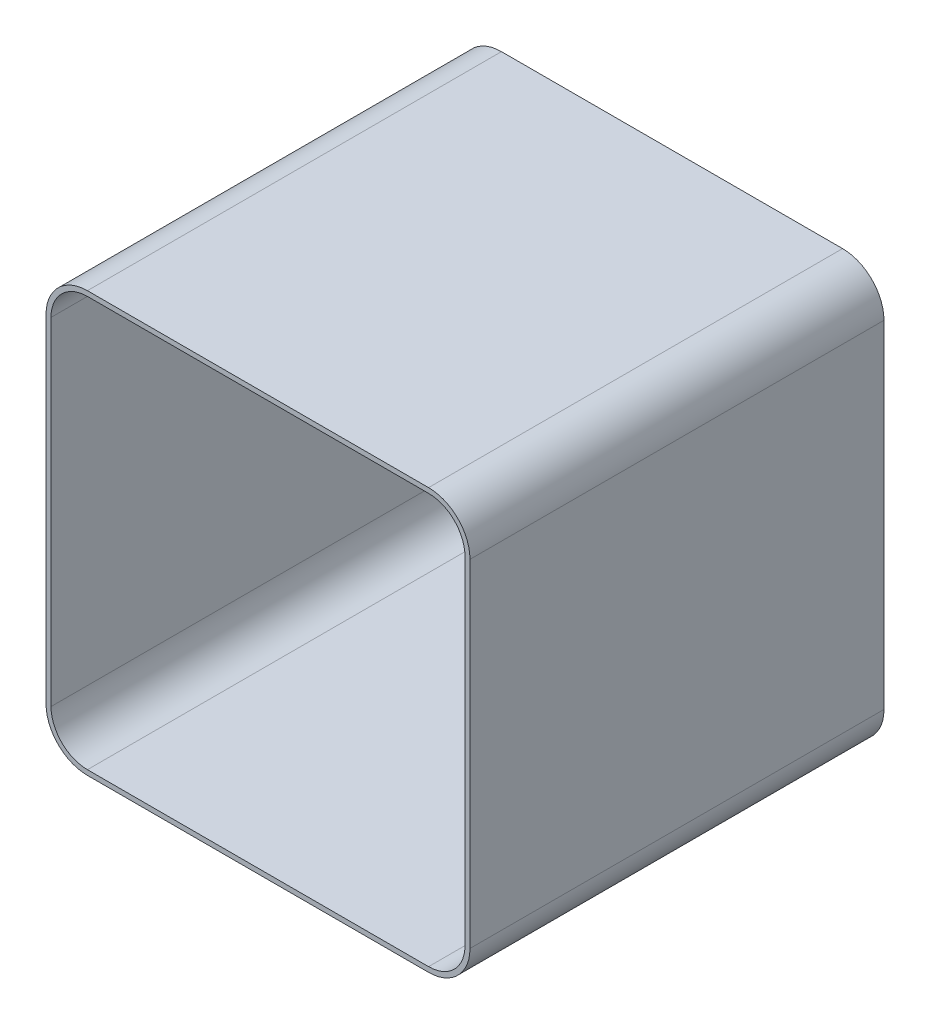
SolidWorks part; units mm, degrees
ref_plane "Front Plane" through (0, 0, 0) normal (0, 0, 1) x (1, 0, 0)
ref_plane "Top Plane" through (0, 0, 0) normal (0, 1, 0) x (1, 0, 0)
ref_plane "Right Plane" through (0, 0, 0) normal (1, 0, 0) x (0, 0, -1)
sketch "Sketch1" plane through (0, 0, 0) normal (0, 0, 1) x (1, 0, 0)
  line L1 (-358.8347, 432.2498) -> (53.1653, 432.2498)
  line L2 (-402.8347, 388.2498) -> (-402.8347, -18.7502)
  line L3 (-358.8347, -62.7502) -> (53.1653, -62.7502)
  line L4 (97.1653, 388.2498) -> (97.1653, -18.7502)
  line L5 (-402.8347, 432.2498) -> (97.1653, -62.7502) construction
  line L6 (-402.8347, -62.7502) -> (97.1653, 432.2498) construction
  arc A0 (-402.8347, 388.2498) -> (-358.8347, 432.2498) centre (-358.8347, 388.2498) cw
  arc A1 (-402.8347, -18.7502) -> (-358.8347, -62.7502) centre (-358.8347, -18.7502) ccw
  arc A2 (97.1653, 388.2498) -> (53.1653, 432.2498) centre (53.1653, 388.2498) ccw
  arc A3 (97.1653, -18.7502) -> (53.1653, -62.7502) centre (53.1653, -18.7502) cw
  point P4 (-152.8347, 184.7498)
  point P18 (-1437.3267, 203.9266)
  dimension "D1" = 44
  dimension "D2" = 44
  dimension "D3" = 44
extrude "Extrude-Thin1" add sketch "Sketch1" along normal blind 500 thin thin type one direction wall 6
